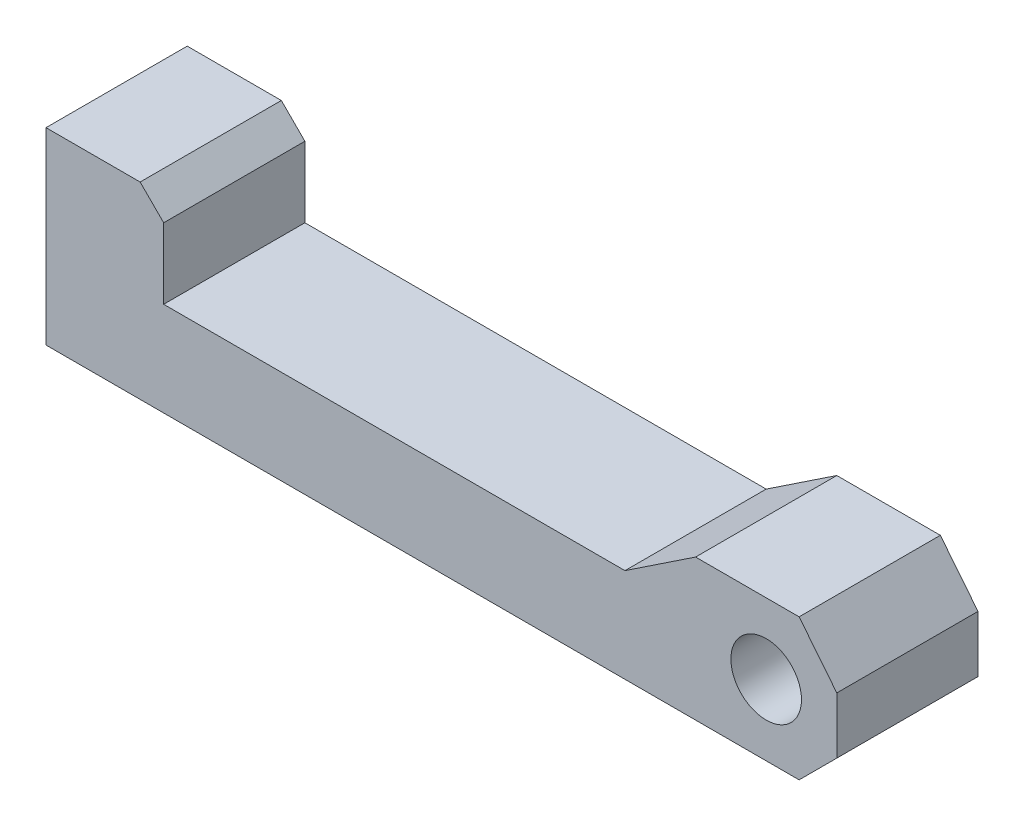
SolidWorks part; units mm, degrees
ref_plane "Front Plane" through (0, 0, 0) normal (0, 0, 1) x (1, 0, 0)
ref_plane "Top Plane" through (0, 0, 0) normal (0, 1, 0) x (1, 0, 0)
ref_plane "Right Plane" through (0, 0, 0) normal (1, 0, 0) x (0, 0, -1)
sketch "Sketch1" plane through (0, 0, 0) normal (0, 1, 0) x (1, 0, 0)
  line L1 (-8.4, -1.5) -> (8.4, -1.5)
  line L2 (-8.4, -1.5) -> (-8.4, 1.5)
  line L3 (-8.4, 1.5) -> (8.4, 1.5)
  line L4 (8.4, -1.5) -> (8.4, 1.5)
  line L5 (-8.4, -1.5) -> (8.4, 1.5) construction
  line L6 (-8.4, 1.5) -> (8.4, -1.5) construction
  point P0 (0, 0)
  dimension "D1" = 16.8
  dimension "D2" = 3
extrude "Boss-Extrude1" add sketch "Sketch1" along normal blind 2
sketch "Sketch2" plane through (0, 2, 0) normal (0, 1, 0) x (1, 0, 0)
  line L0 (-8.4, -1.5) -> (8.4, -1.5) construction
  line L1 (7.6, 1.5) -> (5.4, 1.5)
  line L2 (7.6, 1.5) -> (7.6, -1.5)
  line L3 (7.6, -1.5) -> (5.4, -1.5)
  line L4 (5.4, 1.5) -> (5.4, -1.5)
  line L5 (8.4, -1.5) -> (8.4, 1.5) construction
  dimension "D1" = 3
  dimension "D2" = 0.8
extrude "Boss-Extrude2" add sketch "Sketch2" along normal blind 1
sketch "Sketch6" plane through (0, 0, 1.5) normal (0, 0, 1) x (1, 0, 0)
  line L0 (5.4, 3) -> (3.9, 2)
  line L1 (-8.4, 2) -> (5.4, 2) construction
  line L2 (3.9, 2) -> (5.4, 2)
  line L3 (5.4, 2) -> (5.4, 3)
  line L4 (7.6, 3) -> (7.6, 2)
  line L5 (7.6, 2) -> (8.4, 2)
  line L6 (8.4, 2) -> (7.6, 3)
  dimension "D1" = 1.5
extrude "Boss-Extrude4" add sketch "Sketch6" against normal up to surface (3 mm away) up to face at (3.25, 1.75, -1.5)
hole_wizard "Ø1.5 (1.5) Diameter Hole1" positions "Sketch3" profile "Sketch4" hole size "Ø1.5" standard "DIN" end condition through all
sketch "Sketch3" plane through (0, 0, 1.5) normal (0, 0, 1) x (1, 0, 0)
  line L0 (-8.4, 0) -> (8.4, 0) construction
  line L1 (8.4, 2) -> (8.4, 0) construction
  point P0 (6.9, 1.5)
  dimension "D1" = 1.5
  dimension "D2" = 1.5
sketch "Sketch4" plane through (6.9, 1.5, 1.5) normal (1, 0, 0) x (0, -1, 0)
  line L0 (0, 0) -> (0, 3)
  line L1 (0, 3) -> (0.75, 3)
  line L2 (0.75, 3) -> (0.75, 0)
  line L5 (0.75, 0) -> (0, 0)
  line L11 (0, -6.35) -> (0, 107.95) construction
  dimension "Thru Hole Dia." = 1.5
  dimension "Thru Hole Depth" = 3
sketch "Sketch8" plane through (0, 0, 1.5) normal (0, 0, 1) x (1, 0, 0)
  line L0 (8.4, 0) -> (7.6, 0)
  line L1 (-8.4, 0) -> (8.4, 0) construction
  line L2 (7.6, 0) -> (8.4, 0.8)
  line L3 (8.4, 2) -> (8.4, 0) construction
  line L4 (8.4, 0.8) -> (8.4, 0)
  dimension "D1" = 0.8
  dimension "D2" = 0.8
extrude "Cut-Extrude1" cut sketch "Sketch8" against normal up to surface (3 mm away) up to face at (7.65, 1.5, -1.5)
sketch "Sketch9" plane through (0, 2, 0) normal (0, 1, 0) x (1, 0, 0)
  line L0 (3.9, 1.5) -> (-8.4, 1.5) construction
  line L1 (-8.4, -1.5) -> (-5.9, -1.5)
  line L2 (-8.4, -1.5) -> (-8.4, 1.5)
  line L3 (-8.4, 1.5) -> (-5.9, 1.5)
  line L4 (-5.9, -1.5) -> (-5.9, 1.5)
  dimension "D1" = 2.5
extrude "Boss-Extrude5" add sketch "Sketch9" along normal blind 2
sketch "Sketch10" plane through (0, 0, 1.5) normal (0, 0, 1) x (1, 0, 0)
  line L0 (-5.9, 4) -> (-5.9, 3.5)
  line L1 (-5.9, 4) -> (-5.9, 2) construction
  line L2 (-5.9, 3.5) -> (-6.4, 4)
  line L3 (-8.4, 4) -> (-5.9, 4) construction
  line L4 (-6.4, 4) -> (-5.9, 4)
  dimension "D1" = 0.5
  dimension "D2" = 0.5
extrude "Cut-Extrude2" cut sketch "Sketch10" against normal through all
equation "\"D2@Sketch8\"=\"D1@Sketch8\""
equation "\"D2@Sketch10\"=\"D1@Sketch10\""
